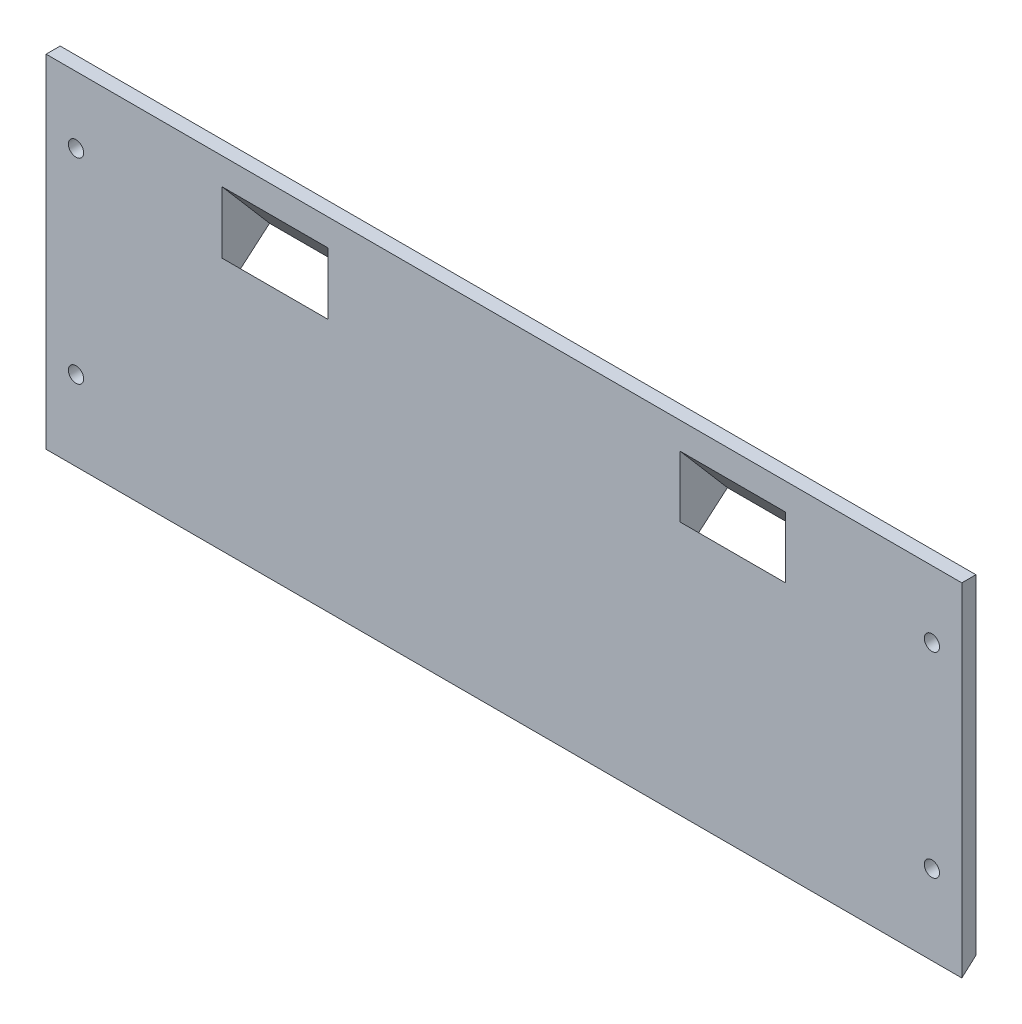
SolidWorks part; units mm, degrees
ref_plane "Alzado" through (0, 0, 0) normal (0, 0, 1) x (1, 0, 0)
ref_plane "Planta" through (0, 0, 0) normal (0, 1, 0) x (1, 0, 0)
ref_plane "Vista lateral" through (0, 0, 0) normal (1, 0, 0) x (0, 0, -1)
sketch "Croquis1" plane through (0, 0, 0) normal (0, 0, 1) x (1, 0, 0)
  line L0 (-97.5, 0) -> (97.5, 0)
  line L1 (97.5, 0) -> (97.5, 38)
  line L2 (97.5, 38) -> (-97.5, 38)
  line L3 (0, 0) -> (0, 28.0598) construction
  line L4 (-97.5, 0) -> (-97.5, 38)
  circle A2 centre (91.125, 15) radius 1.625
  circle A3 centre (-91.125, 15) radius 1.625
  point P13 (0, 38)
  point P14 (0, 0)
  dimension "D1" = 3.25
  dimension "D2" = 15
  dimension "D3" = 97.5
  dimension "D4" = 38
  dimension "D5" = 6.375
extrude "Saliente-Extruir1" add sketch "Croquis1" along normal blind 3
sketch "Croquis8" plane through (0, 0, 0) normal (0, -1, 0) x (1, 0, 0)
  line L1 (-97.5, 3) -> (97.5, 3)
  line L2 (-97.5, 3) -> (-97.5, 0)
  line L3 (-97.5, 0) -> (97.5, 0)
  line L4 (97.5, 3) -> (97.5, 0)
extrude "Saliente-Extruir5" add sketch "Croquis8" along normal blind 5
sketch "Croquis9" plane through (0, 38, 0) normal (0, 1, 0) x (1, 0, 0)
  line L1 (-97.5, 0) -> (97.5, 0)
  line L2 (-97.5, 0) -> (-97.5, -3)
  line L3 (-97.5, -3) -> (97.5, -3)
  line L4 (97.5, 0) -> (97.5, -3)
extrude "Saliente-Extruir6" add sketch "Croquis9" along normal blind 5
sketch "Croquis10" plane through (97.5, 0, 0) normal (1, 0, 0) x (0, 0, -1)
  line L0 (0, 35.3168) -> (11.1006, 22.3656)
  line L1 (1.23, 13.9055) -> (0, 12.8513)
  line L2 (0, 35.3168) -> (0, 12.8513)
  line L3 (0, -5) -> (0, 43) construction
  line L4 (11.1006, 22.3656) -> (1.23, 13.9055)
  line L6 (-3, 18.8408) -> (0, 15.3406) construction
  line L7 (-3, -5) -> (-3, 43) construction
  line L8 (-3, 18.8408) -> (5.5756, 26.191) construction
  dimension "D1" = 5
  dimension "D2" = 6.5
  dimension "D3" = 14.62
  dimension "D4" = 40.6
extrude "Saliente-Extruir7" add sketch "Croquis10" against normal blind 35 from offset 35 offset against normal yes
sketch "Croquis11" plane through (0, 7.4087, 6.35) normal (0, -0.7593, -0.6508) x (1, 0, 0)
  line L3 (60, -13.4833) -> (37.5, -13.4833)
  line L6 (37.5, -13.4833) -> (37.5, -21.9833)
  line L7 (37.5, -21.9833) -> (60, -21.9833)
  line L8 (60, -21.9833) -> (60, -13.4833)
  line L9 (62.5, -8.3633) -> (62.5, -22.9833) construction
  line L10 (27.5, -22.9833) -> (62.5, -22.9833) construction
  dimension "D1" = 8.5
  dimension "D2" = 22.5
  dimension "D3" = 2.5
  dimension "D4" = 1
extrude "Cortar-Extruir4" cut sketch "Croquis11" against normal through all both and the other way through all
sketch "Croquis12" plane through (62.5, 0, 0) normal (1, 0, 0) x (0, 0, -1)
  line L0 (11.1006, 22.3656) -> (0, 12.8513)
  line L1 (0, 12.8513) -> (0, 19.4365)
  line L2 (0, -5) -> (0, 43) construction
  line L3 (0, 19.4365) -> (7.8467, 26.162)
  line L4 (11.1006, 22.3656) -> (0, 35.3168) construction
  line L5 (7.8467, 26.162) -> (11.1006, 22.3656)
  dimension "D1" = 5
extrude "Cortar-Extruir5" cut sketch "Croquis12" against normal up to next
sketch "Croquis13" plane through (0, 11.205, 9.6039) normal (0, -0.7593, -0.6508) x (1, 0, 0)
  line L0 (27.5, -12.6488) -> (27.5, -22.9833) construction
  line L3 (27.5, -22.9833) -> (62.5, -22.9833) construction
  circle A0 centre (33.75, -17.8233) radius 1
  dimension "D1" = 2
  dimension "D3" = 5.16
  dimension "D2" = 6.25
extrude "Cortar-Extruir6" cut sketch "Croquis13" against normal blind 5
sketch "Croquis14" plane through (-97.5, 0, 0) normal (-1, 0, 0) x (0, 0, 1)
  line L0 (0, 19.4365) -> (-7.8467, 26.162)
  line L1 (-7.8467, 26.162) -> (0, 35.3168)
  line L2 (0, 35.3168) -> (0, 19.4365)
extrude "Saliente-Extruir8" add sketch "Croquis14" against normal blind 35 from offset 35 offset against normal yes
sketch "Croquis16" plane through (0, 11.205, 9.6039) normal (0, -0.7593, -0.6508) x (1, 0, 0)
  line L0 (0, 0) -> (0, -29.2293) construction
  line L5 (-37.5, -21.9833) -> (-60, -21.9833)
  line L6 (-60, -13.411) -> (-60, -21.9833)
  line L8 (-37.5, -13.411) -> (-60, -13.411)
  line L9 (60, -21.9833) -> (37.5, -21.9833) construction
  line L10 (-37.5, -13.411) -> (-37.5, -21.9833)
  line L11 (-62.5, -22.9833) -> (-62.5, -12.6488) construction
  dimension "D1" = 22.5
  dimension "D2" = 2.5
extrude "Cortar-Extruir7" cut sketch "Croquis16" against normal through all both and the other way through all
sketch "Croquis17" plane through (0, 11.205, 9.6039) normal (0, -0.7593, -0.6508) x (1, 0, 0)
  line L0 (0, 0) -> (0, -24) construction
  line L1 (-27.5, -22.9833) -> (-62.5, -22.9833) construction
  line L3 (-37.5, -21.9833) -> (-37.5, -13.411) construction
  circle A1 centre (-33.75, -17.8233) radius 1
  dimension "D1" = 5.16
  dimension "D2" = 3.75
extrude "Cortar-Extruir8" cut sketch "Croquis17" against normal blind 5
sketch "Croquis18" plane through (0, 0, 3) normal (0, 0, 1) x (1, 0, 0)
  line L0 (-97.5, 19) -> (97.5, 19) construction
  circle A2 centre (91.125, 23) radius 1.625
  circle A3 centre (-91.125, 23) radius 1.625
extrude "Cortar-Extruir9" cut sketch "Croquis18" against normal blind 10
sketch "Croquis19" plane through (0, 0, 3) normal (0, 0, 1) x (1, 0, 0)
  line L0 (-97.5, 43) -> (-97.5, -5) construction
  line L1 (-97.5, 19) -> (97.5, 19)
  line L2 (-97.5, 19) -> (-97.5, -5)
  line L3 (-97.5, -5) -> (97.5, -5)
  line L4 (97.5, 19) -> (97.5, -5)
extrude "Saliente-Extruir9" add sketch "Croquis19" against normal up to vertex (3 mm away) up to point (-97.5, -5, 0)
sketch "Croquis20" plane through (0, 0, 3) normal (0, 0, 1) x (1, 0, 0)
  line L0 (-97.5, 43) -> (97.5, 43) construction
  line L1 (-97.5, -5) -> (97.5, -5)
  line L2 (-97.5, -5) -> (-97.5, -33.69)
  line L3 (-97.5, -33.69) -> (97.5, -33.69)
  line L4 (97.5, -5) -> (97.5, -33.69)
  dimension "D1" = 76.69
extrude "Saliente-Extruir10" add sketch "Croquis20" against normal up to vertex (3 mm away) up to point (-97.5, -5, 0)
sketch "Croquis22" plane through (0, 0, 3) normal (0, 0, 1) x (1, 0, 0)
  line L0 (-97.5, 43) -> (-97.5, -33.69) construction
  line L1 (-97.5, 43) -> (97.5, 43)
  line L2 (-97.5, 43) -> (-97.5, 51.7993)
  line L3 (-97.5, 51.7993) -> (97.5, 51.7993)
  line L4 (97.5, 43) -> (97.5, 51.7993)
  line L5 (-97.5, 27.545) -> (-86.6825, 27.545)
  line L6 (-97.5, 27.545) -> (-97.5, 18.136)
  line L7 (-97.5, 18.136) -> (-86.6825, 18.136)
  line L8 (-86.6825, 27.545) -> (-86.6825, 18.136)
  line L9 (97.5, -33.69) -> (97.5, 43) construction
  line L10 (86.4429, 27.545) -> (97.5, 27.545)
  line L11 (86.4429, 27.545) -> (86.4429, 18.136)
  line L12 (86.4429, 18.136) -> (97.5, 18.136)
  line L13 (97.5, 27.545) -> (97.5, 18.136)
extrude "Saliente-Extruir11" add sketch "Croquis22" against normal up to vertex (3 mm away) up to point (-97.5, -33.69, 0)
sketch "Croquis23" plane through (0, 0, 3) normal (0, 0, 1) x (1, 0, 0)
  line L1 (-97.5, 51.7993) -> (-97.5, -33.69) construction
  line L2 (97.5, 51.7993) -> (-97.5, 51.7993) construction
  line L3 (0, -1.1555) -> (0, 35.7449) construction
  circle A0 centre (-91.125, 28.7993) radius 1.625
  circle A1 centre (-91.125, -12.8907) radius 1.625
  circle A2 centre (91.125, -12.8907) radius 1.625
  circle A3 centre (91.125, 28.7993) radius 1.625
  dimension "D1" = 6.375
  dimension "D2" = 23
  dimension "D3" = 41.69
  dimension "D4" = 3.25
extrude "Cortar-Extruir10" cut sketch "Croquis23" against normal blind 10
sketch "Croquis25" plane through (-97.5, 0, 0) normal (-1, 0, 0) x (0, 0, 1)
  line L0 (0, 51.7993) -> (0, -33.69) construction
  line L1 (0, -27.2007) -> (6.0483, -27.2007)
  line L2 (0, -27.2007) -> (0, -41.7759)
  line L3 (0, -41.7759) -> (6.0483, -41.7759)
  line L4 (6.0483, -27.2007) -> (6.0483, -41.7759)
  line L5 (0, 51.7993) -> (3, 51.7993) construction
  dimension "D1" = 79
extrude "Cortar-Extruir11" cut sketch "Croquis25" against normal through all both and the other way through all
sketch "Croquis26" plane through (97.5, 0, 0) normal (1, 0, 0) x (0, 0, -1)
  line L0 (0, 51.7993) -> (0, 57.173)
  line L1 (0, 57.173) -> (3, 57.173)
  line L2 (3, 57.173) -> (3, 48.7993)
  line L3 (3, 48.7993) -> (0, 44.7993)
  line L4 (0, -27.2007) -> (0, 51.7993) construction
  line L5 (0, 51.7993) -> (-3, 51.7993) construction
  line L6 (0, 51.7993) -> (0, 44.7993)
  dimension "D1" = 3
  dimension "D2" = 7
  dimension "D3" = 3
extrude "Saliente-Extruir12" add sketch "Croquis26" against normal blind 65 from offset 65 offset against normal yes
sketch "Croquis29" plane through (97.5, 0, 0) normal (1, 0, 0) x (0, 0, -1)
  line L0 (-3, -27.2007) -> (21.0476, -55.2576)
  line L1 (-3, -27.2007) -> (-1.1795, -25.6404)
  line L2 (21.0476, -55.2576) -> (22.8681, -53.6972)
  line L3 (-1.1795, -25.6404) -> (22.8681, -53.6972)
  line L4 (7.8467, 26.162) -> (0, 35.3168) construction
  dimension "D1" = 35
extrude "Saliente-Extruir15" add sketch "Croquis29" against normal blind 12.75
sketch "Croquis30" plane through (-97.5, 0, 0) normal (-1, 0, 0) x (0, 0, 1)
  line L0 (0, -27.2007) -> (3, -27.2007)
  line L1 (3, -27.2007) -> (-21.0476, -55.2576)
  line L2 (-21.0476, -55.2576) -> (-22.8681, -53.6972)
  line L3 (-22.8681, -53.6972) -> (0, -27.2007)
extrude "Saliente-Extruir16" add sketch "Croquis30" against normal blind 12.75
sketch "Croquis27" plane through (97.5, 0, 0) normal (1, 0, 0) x (0, 0, -1)
  line L1 (-3, -27.2007) -> (0, -27.2007)
  line L2 (-3, -27.2007) -> (-3, -57.2007)
  line L3 (-3, -57.2007) -> (0, -57.2007)
  line L4 (0, -27.2007) -> (0, -57.2007)
  dimension "D1" = 30
extrude "Saliente-Extruir13" add sketch "Croquis27" against normal blind 195
sketch "Croquis28" plane through (97.5, 0, 0) normal (1, 0, 0) x (0, 0, -1)
  line L0 (0, -52.2007) -> (20.7233, -76.379)
  line L1 (0, -52.2007) -> (-3, -54.772)
  line L2 (20.7233, -76.379) -> (16.2045, -80.252)
  line L4 (0, -57.2007) -> (0, -30.7009) construction
  line L5 (7.8467, 26.162) -> (0, 35.3168) construction
  line L6 (-3, -57.2007) -> (0, -57.2007) construction
  line L7 (-3, -57.2007) -> (16.5232, -79.9789)
  line L8 (-3, -54.772) -> (-3, -57.2007)
  line L9 (-3, -57.2007) -> (-3, 51.7993) construction
  line M6 (-3, 51.7993) -> (-3, -57.2007)
  line M7 (-3, -57.2007) -> (0, -57.2007)
  line M8 (0, -57.2007) -> (0, -30.7009)
  dimension "D1" = 5
  dimension "D2" = 30
extrude "Saliente-Extruir14" add sketch "Croquis28" against normal blind 195 contours L7 L2 L0 M7 M8 | L1 M8 M6 M7 region at (97.5, -55.2694, 1.3269) region at (97.5, -66.9176, -9.0188)
sketch "Croquis31" plane through (0, -13.002, 15.1697) normal (0, -0.6508, 0.7593) x (1, 0, 0)
  line L1 (0, 0) -> (0, -106.5046) construction
  line L2 (97.5, -20.5129) -> (84.75, -20.5129) construction
  circle A0 centre (91.125, -37.9629) radius 1.625
  circle A1 centre (-91.125, -37.9629) radius 1.625
  dimension "D1" = 3.25
  dimension "D2" = 17.45
extrude "Cortar-Extruir12" cut sketch "Croquis31" against normal through all both and the other way through all
sketch "Croquis32" plane through (97.5, 0, 0) normal (1, 0, 0) x (0, 0, -1)
  line L0 (0, -30.7009) -> (21.0476, -55.2576)
  line L1 (21.0476, -55.2576) -> (10.3616, -64.2899)
  line L2 (0, -52.2007) -> (20.7233, -76.379) construction
  line L3 (10.3616, -64.2899) -> (0, -52.2007)
  line L4 (0, -52.2007) -> (0, -30.7009)
extrude "Saliente-Extruir17" add sketch "Croquis32" against normal blind 12.75
sketch "Croquis33" plane through (-97.5, 0, 0) normal (-1, 0, 0) x (0, 0, 1)
  line L0 (0, -30.7009) -> (0, -52.2007)
  line L1 (0, -52.2007) -> (-10.3616, -64.2899)
  line L2 (-10.3616, -64.2899) -> (-21.0476, -55.2576)
  line L3 (-21.0476, -55.2576) -> (0, -30.7009)
extrude "Saliente-Extruir18" add sketch "Croquis33" against normal blind 12.75
sketch "Croquis39" plane through (0, -11.4417, 13.3493) normal (0, 0.6508, -0.7593) x (-1, 0, 0)
  circle A0 centre (91.125, -37.9629) radius 1.625
  circle A1 centre (-91.125, -37.9629) radius 1.625
extrude "Cortar-Extruir15" cut sketch "Croquis39" against normal through all both and the other way through all
sketch "Croquis40" plane through (0, -11.4417, 13.3493) normal (0, 0.6508, -0.7593) x (-1, 0, 0)
  circle A0 centre (-91.125, -37.9629) radius 4
  circle A1 centre (91.125, -37.9629) radius 4
  dimension "D1" = 8
  dimension "D2" = 8
extrude "Cortar-Extruir16" cut sketch "Croquis40" against normal through all from offset 4 offset against normal yes
sketch "Croquis43" plane through (0, -54.2716, -46.5164) normal (0, -0.7593, -0.6508) x (1, 0, 0)
  line L0 (-97.5, 33.9709) -> (97.5, 33.9709) construction
  line L1 (-10, 33.9709) -> (10, 33.9709)
  line L2 (-10, 33.9709) -> (-10, 23.9709)
  line L3 (-10, 23.9709) -> (-3.75, 23.9709)
  line L4 (10, 33.9709) -> (10, 23.9709)
  line L5 (-3.75, 28.9709) -> (-3.75, 23.9709)
  line L7 (3.75, 23.9709) -> (3.75, 28.9709)
  line L8 (3.75, 23.9709) -> (10, 23.9709)
  arc A0 (3.75, 28.9709) -> (-3.75, 28.9709) centre (0, 28.9709) ccw
  dimension "D4" = 7.5
  dimension "D5" = 5
  dimension "D1" = 10
  dimension "D2" = 20
  dimension "D3" = 10
extrude "Saliente-Extruir19" add sketch "Croquis43" against normal blind 4 from offset 15 offset against normal yes
chamfer "Chaflán1" distance 10 angle 45 2 edges at (-10, -63.4714, -9.6601) (10, -63.4714, -9.6601)
sketch "Croquis44" plane through (-97.5, 0, 0) normal (-1, 0, 0) x (0, 0, 1)
  line L0 (0, 51.7993) -> (0, 44.7993)
  line L1 (0, 44.7993) -> (-5.4965, 48.2993)
  line L2 (-5.4965, 48.2993) -> (-4.8056, 58.7087)
  line L3 (-4.8056, 58.7087) -> (3.3468, 60.1858)
  line L4 (3.3468, 60.1858) -> (0, 51.7993)
  line L5 (0, -27.2007) -> (19.9404, -44.9682)
  line L6 (19.9404, -44.9682) -> (-20.5731, -90.4365)
  line L7 (-20.5731, -90.4365) -> (-48.0078, -62.5188)
  line L8 (-48.0078, -62.5188) -> (0, -27.0166)
  line L9 (0, -27.2007) -> (0, -27.0166)
  line M1 (-22.8681, -53.6972) -> (-21.0476, -55.2576)
  line M2 (-21.0476, -55.2576) -> (-10.3616, -64.2899)
  line M3 (-10.3616, -64.2899) -> (-20.7233, -76.379)
  line M4 (-20.7233, -76.379) -> (-16.5232, -79.9789)
  line M5 (-16.5232, -79.9789) -> (3, -57.2007)
  line M6 (3, -57.2007) -> (3, 51.7993)
  line M8 (0, 51.7993) -> (0, -27.2007)
  line M9 (0, -27.2007) -> (-22.8681, -53.6972)
extrude "Cortar-Extruir17" cut sketch "Croquis44" against normal through all both and the other way through all contours L4 L3 L2 L1 M8 | L8 L7 L6 L5 M6 M5 M4 M3 M2 M1 M9 M8 | L9 L8 L7 L6 L5 region at (-97.5, -60.3752, -16.5833) region at (-97.5, 53.4011, -1.8476)
sketch "Croquis45" plane through (-97.5, 0, 0) normal (-1, 0, 0) x (0, 0, 1)
  line L0 (3, 51.7993) -> (0, 51.7993)
  line L1 (3, 51.7993) -> (3, 43)
  line L2 (0, 51.7993) -> (0, 43)
  line L3 (3, 43) -> (0, 43)
  line L4 (0, 35.3168) -> (-7.8467, 26.162) construction
  dimension "D1" = 5
extrude "Cortar-Extruir18" cut sketch "Croquis45" against normal through all
